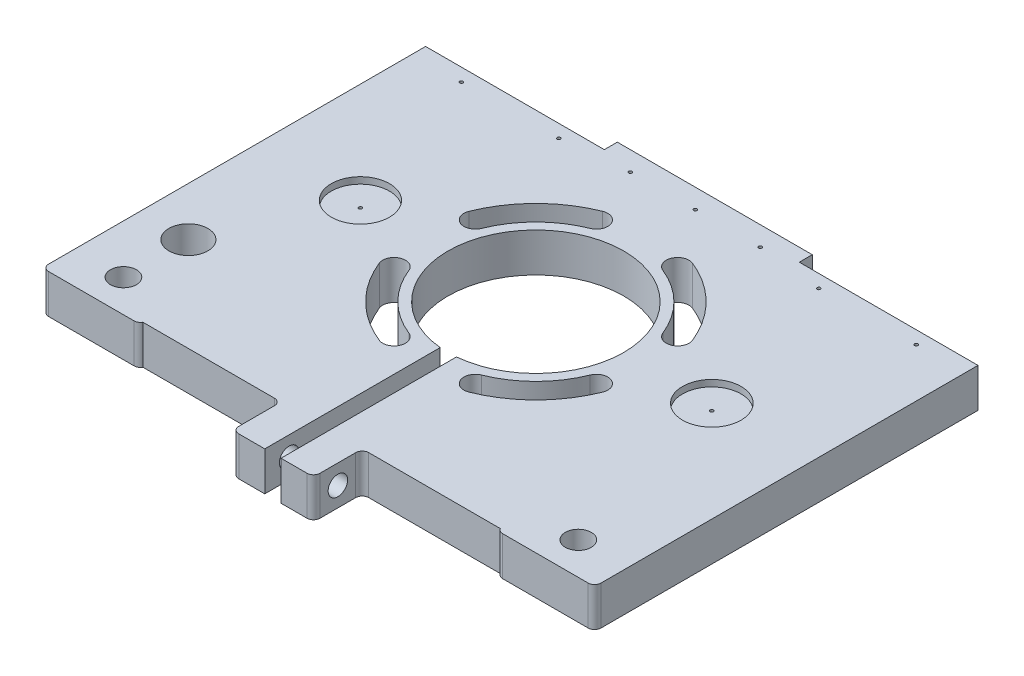
SolidWorks part; units mm, degrees
ref_plane "Front Plane" through (0, 0, 0) normal (0, 0, 1) x (1, 0, 0)
ref_plane "Top Plane" through (0, 0, 0) normal (0, 1, 0) x (1, 0, 0)
ref_plane "Right Plane" through (0, 0, 0) normal (1, 0, 0) x (0, 0, -1)
sketch "Sketch1" plane through (0, 0, 0) normal (0, 1, 0) x (1, 0, 0)
  line L0 (55, 122) -> (55, 118)
  line L1 (55, 118) -> (0, 118)
  line L2 (115, 118) -> (170, 118)
  line L3 (115, 122) -> (115, 118)
  line L4 (0, 114) -> (170, 114) construction
  line L5 (15, 10) -> (15, 30) construction
  line L25 (85, 122) -> (85, 0.4842) construction
  line L26 (55, 122) -> (115, 122)
  line L27 (0, 118) -> (0, 0)
  line L28 (0, 0) -> (30, 0)
  line L29 (170, 118) -> (170, 0)
  line L30 (0, 66.9342) -> (170, 66.9342) construction
  line L31 (30, 0) -> (30, 1)
  line L32 (30, 1) -> (72.5, 1)
  line L33 (72.5, 1) -> (72.5, -14)
  line L34 (72.5, -14) -> (82.5, -14)
  line L35 (82.5, -14) -> (82.5, 40)
  line L36 (0, 20) -> (170, 20) construction
  line L37 (87.5, -14) -> (87.5, 40)
  line L38 (97.5, 1) -> (97.5, -14)
  line L39 (97.5, -14) -> (87.5, -14)
  line L40 (140, 1) -> (97.5, 1)
  line L41 (140, 0) -> (140, 1)
  line L42 (140, 0) -> (170, 0)
  line L43 (155, 0) -> (155, 20) construction
  line L44 (0, 116) -> (170, 116) construction
  circle A0 centre (65, 116) radius 0.5
  circle A1 centre (105, 116) radius 0.5
  circle A2 centre (45, 114) radius 0.5
  circle A3 centre (15, 114) radius 0.5
  circle A4 centre (155, 114) radius 0.5
  circle A5 centre (125, 114) radius 0.5
  circle A6 centre (15, 30) radius 6
  arc A26 (87.5, 40) -> (82.5, 40) centre (85, 66.9342) ccw
  circle A27 centre (155, 10) radius 4
  circle A28 centre (15, 10) radius 4
  arc A29 (53.8656, 79.4342) -> (72.5, 98.0687) centre (85, 66.9342) cw construction
  arc A30 (71.196, 101.3167) -> (50.6176, 80.7382) centre (85, 66.9342) ccw
  arc A31 (73.804, 94.8206) -> (57.1136, 78.1302) centre (85, 66.9342) ccw
  arc A32 (73.804, 94.8206) -> (71.196, 101.3167) centre (72.5, 98.0687) ccw
  arc A33 (50.6176, 80.7382) -> (57.1136, 78.1302) centre (53.8656, 79.4342) ccw
  arc A34 (116.1344, 79.4342) -> (97.5, 98.0687) centre (85, 66.9342) ccw construction
  arc A35 (98.804, 101.3167) -> (119.3824, 80.7382) centre (85, 66.9342) cw
  arc A36 (96.196, 94.8206) -> (112.8864, 78.1302) centre (85, 66.9342) cw
  arc A37 (96.196, 94.8206) -> (98.804, 101.3167) centre (97.5, 98.0687) cw
  arc A38 (119.3824, 80.7382) -> (112.8864, 78.1302) centre (116.1344, 79.4342) cw
  arc A39 (53.8656, 54.4342) -> (72.5, 35.7998) centre (85, 66.9342) ccw construction
  arc A40 (71.196, 32.5518) -> (50.6176, 53.1302) centre (85, 66.9342) cw
  arc A41 (73.804, 39.0478) -> (57.1136, 55.7382) centre (85, 66.9342) cw
  arc A42 (73.804, 39.0478) -> (71.196, 32.5518) centre (72.5, 35.7998) cw
  arc A43 (50.6176, 53.1302) -> (57.1136, 55.7382) centre (53.8656, 54.4342) cw
  arc A44 (116.1344, 54.4342) -> (97.5, 35.7998) centre (85, 66.9342) cw construction
  arc A45 (98.804, 32.5518) -> (119.3824, 53.1302) centre (85, 66.9342) ccw
  arc A46 (96.196, 39.0478) -> (112.8864, 55.7382) centre (85, 66.9342) ccw
  arc A47 (96.196, 39.0478) -> (98.804, 32.5518) centre (97.5, 35.7998) ccw
  arc A48 (119.3824, 53.1302) -> (112.8864, 55.7382) centre (116.1344, 54.4342) ccw
  circle A49 centre (85, 116) radius 0.5
  point P81 (85, 66.9342)
  point P84 (155, 10)
  point P108 (61.2766, 90.6577)
  point P115 (108.7234, 90.6577)
  point P122 (61.2766, 43.2108)
  point P129 (108.7234, 43.2108)
  point P134 (85, 116)
  dimension "D4" = 4
  dimension "D9" = 12
  dimension "D11" = 1
  dimension "D25" = 54.1
  dimension "D31" = 8
  dimension "D35" = 7
  dimension "D36" = 3
  dimension "D37" = 18
  dimension "D38" = 18
  dimension "D39" = 1
  dimension "D1" = 60
  dimension "D5" = 20
  dimension "D6" = 20
  dimension "D7" = 30
  dimension "D8" = 4
  dimension "D10" = 20
  dimension "D23" = 122
  dimension "D24" = 170
  dimension "D26" = 30
  dimension "D27" = 20
  dimension "D28" = 5
  dimension "D29" = 15
  dimension "D32" = 20
  dimension "D33" = 6
  dimension "D34" = 10
extrude "Boss-Extrude1" add sketch "Sketch1" along normal blind 12
sketch "Sketch2" plane through (0, 12, 0) normal (0, 1, 0) x (1, 0, 0)
  line L0 (85, 66.9342) -> (0, 66.9342) construction
  line L1 (115, 122) -> (55, 122) construction
  line L2 (170, 0) -> (170, 118) construction
  line L4 (85, -95.05) -> (85, 122) construction
  line L7 (85, 66.9342) -> (170, 66.9342) construction
  circle A0 centre (31, 66.9342) radius 8.95
  circle A1 centre (139.15, 66.9342) radius 9
  arc A3 (87.5, 40) -> (82.5, 40) centre (85, 66.9342) ccw construction
  dimension "D1" = 17.9
  dimension "D2" = 18
  dimension "D3" = 90.2
  dimension "D4" = 72.2
extrude "Cut-Extrude1" cut sketch "Sketch2" against normal blind 2
sketch "Sketch3" plane through (0, 10, 0) normal (0, 1, 0) x (1, 0, 0)
  circle A0 centre (31, 66.9342) radius 0.5
  circle A1 centre (139.15, 66.9342) radius 0.5
  dimension "D1" = 1
extrude "Cut-Extrude2" cut sketch "Sketch3" against normal through all
sketch "Sketch4" plane through (72.5, 0, 0) normal (-1, 0, 0) x (0, 0, 1)
  line L0 (6.5, 12) -> (6.5, 0) construction
  line L3 (14, 6) -> (-1, 6) construction
  line L5 (-1, 12) -> (-1, 0) construction
  line L7 (14, 12) -> (14, 0) construction
  line L8 (-1, 12) -> (14, 12) construction
  line L9 (-1, 0) -> (14, 0) construction
  circle A0 centre (6.5, 6) radius 3
  point P12 (6.5, 6)
  dimension "D1" = 6
extrude "Cut-Extrude3" cut sketch "Sketch4" along direction (-1, 0, 0) on the side against the normal up to surface (25 mm away) up to face at (97.5, 6, 6.5)
fillet "Fillet1" radius 2 8 edges at (170, 6, 0) (140, 6, 0) (72.5, 6, -1) (97.5, 6, -1) (97.5, 6, 14) (72.5, 6, 14) (0, 6, 0) (30, 6, 0)
